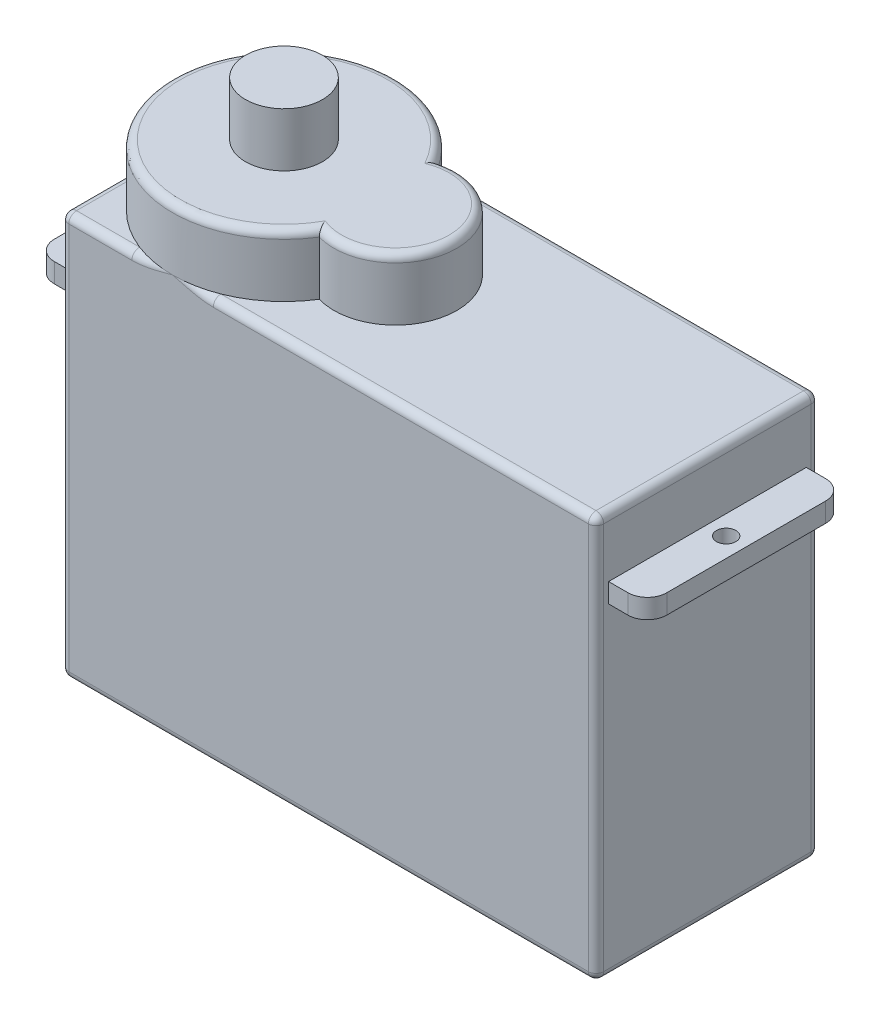
SolidWorks part; units mm, degrees
ref_plane "Front Plane" through (0, 0, 0) normal (0, 0, 1) x (1, 0, 0)
ref_plane "Top Plane" through (0, 0, 0) normal (0, 1, 0) x (1, 0, 0)
ref_plane "Right Plane" through (0, 0, 0) normal (1, 0, 0) x (0, 0, -1)
sketch "Sketch2" plane through (0, 0, 0) normal (0, 1, 0) x (1, 0, 0)
  line L1 (0, 0) -> (27.6, 0)
  line L2 (0, 0) -> (0, 11.5)
  line L3 (0, 11.5) -> (27.6, 11.5)
  line L4 (27.6, 0) -> (27.6, 11.5)
  line L5 (0, 10.8497) -> (-1, 10.8497)
  line L6 (0, 10.8497) -> (0, 0.6497)
  line L7 (0, 0.6497) -> (-1, 0.6497)
  line L8 (-2, 9.8497) -> (-2, 1.6497)
  line L9 (27.6, 10.8497) -> (28.6, 10.8497)
  line L10 (27.6, 10.8497) -> (27.6, 0.6497)
  line L11 (27.6, 0.6497) -> (28.6, 0.6497)
  line L12 (29.6, 9.8497) -> (29.6, 1.6497)
  arc A0 (28.6, 10.8497) -> (29.6, 9.8497) centre (28.6, 9.8497) cw
  arc A1 (29.6, 1.6497) -> (28.6, 0.6497) centre (28.6, 1.6497) cw
  arc A2 (-2, 1.6497) -> (-1, 0.6497) centre (-1, 1.6497) ccw
  arc A3 (-2, 9.8497) -> (-1, 10.8497) centre (-1, 9.8497) cw
  circle A4 centre (-1, 5.7164) radius 0.5
  circle A5 centre (28.6, 5.7164) radius 0.5
  point P15 (29.6, 10.8497)
  point P18 (29.6, 0.6497)
  point P21 (-2, 0.6497)
  point P24 (-2, 10.8497)
  dimension "D9" = 1
  dimension "D10" = 1
  dimension "D11" = 1
  dimension "D1" = 11.5
  dimension "D2" = 31.6
  dimension "D3" = 2
  dimension "D4" = 2
  dimension "D5" = 10.2
  dimension "D6" = 10.2
  dimension "D7" = 0.6503
  dimension "D8" = 0.6497
  dimension "D12" = 29.6
extrude "Boss-Extrude1" add sketch "Sketch2" along normal blind 20.8 contours L1 L4 L3 L2 region at (13.8, 0, -5.75)
sketch "Sketch3" plane through (0, 20.8, 0) normal (0, 1, 0) x (1, 0, 0)
  line L2 (0, 0) -> (0, 11.5) construction
  line L3 (0, 0) -> (27.6, 0) construction
  line L4 (0, 11.5) -> (27.6, 11.5) construction
  circle A0 centre (5.75, 5.75) radius 5.75
  circle A1 centre (11.5, 5.75) radius 3.175
  dimension "D2" = 6.35
extrude "Boss-Extrude2" add sketch "Sketch3" along normal blind 3.175 contours A0 A1 | A1 A0 | A0 A1 region at (10.0075, 20.8, -5.75) region at (12.6772, 20.8, -5.75) region at (5.0887, 20.8, -5.75)
extrude "Boss-Extrude3" add sketch "Sketch2<3>" along normal blind 1 from offset 16.7 contours A3 L8 A2 L7 L2 L5 A4 | A1 L12 A0 L9 L4 L11 A5 region at (-0.5, 0, -0.7536) region at (27.7039, 0, -5.7497)
sketch "Sketch2<3>" plane through (0, 0, 0) normal (0, 1, 0) x (1, 0, 0) same geometry as "Sketch2"
sketch "Sketch4" plane through (0, 23.975, 0) normal (0, 1, 0) x (1, 0, 0)
  circle A0 centre (5.75, 5.75) radius 1.9844
  dimension "D1" = 3.9688
extrude "Boss-Extrude4" add sketch "Sketch4" along normal blind 2.7781
fillet "Fillet1" radius 0.3969 17 edges at (27.6, 0, -5.75) (13.8, 0, -11.5) (0, 0, -5.75) (13.8, 0, 0) (0, 20.8, -8.625) (2.875, 20.8, -11.5) (2.875, 20.8, 0) (0, 20.8, -2.875) (16.675, 20.8, -11.5) (16.675, 20.8, 0) (27.6, 20.8, -5.75) (27.6, 10.4, 0) (27.6, 10.4, -11.5) (0, 10.4, -11.5) (0, 10.4, 0) (14.675, 23.975, -5.75) (0, 23.975, -5.75)
